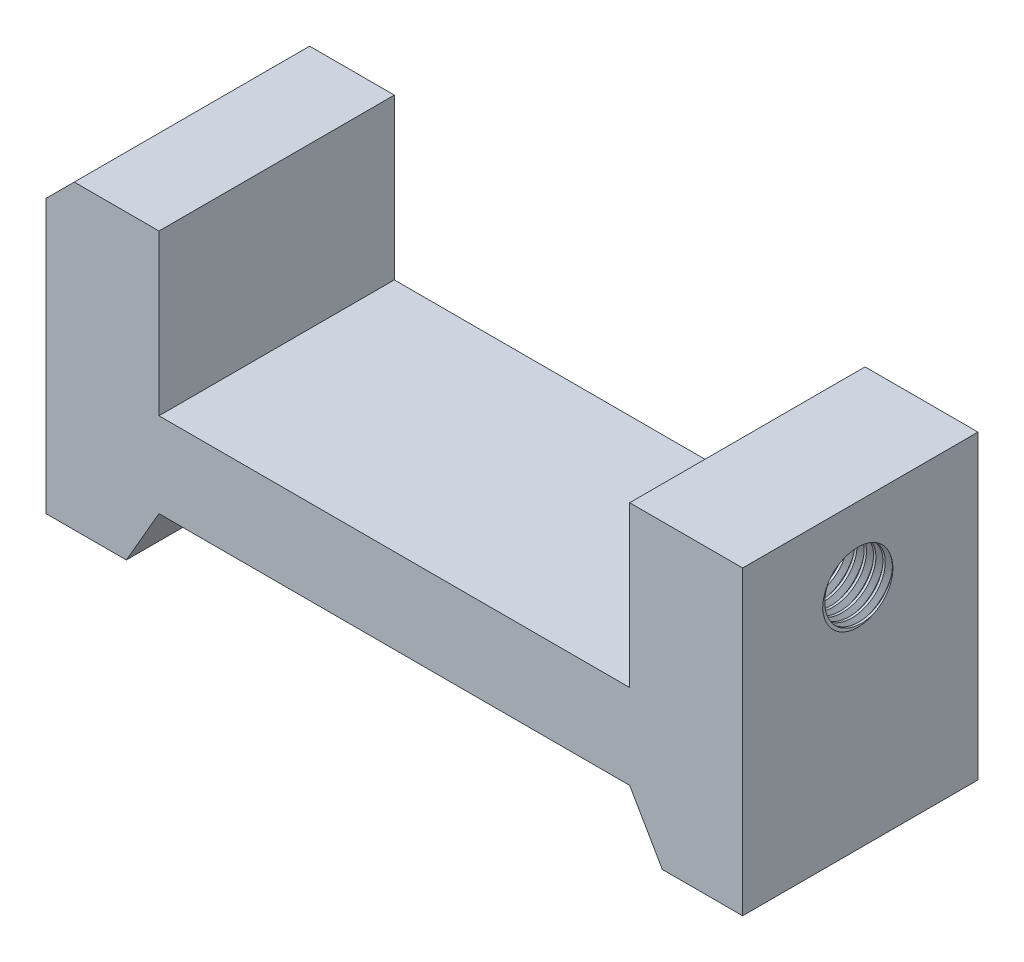
SolidWorks part; units mm, degrees
ref_plane "Front Plane" through (0, 0, 0) normal (0, 0, 1) x (1, 0, 0)
ref_plane "Top Plane" through (0, 0, 0) normal (0, 1, 0) x (1, 0, 0)
ref_plane "Right Plane" through (0, 0, 0) normal (1, 0, 0) x (0, 0, -1)
sketch "Sketch1" plane through (0, 0, 0) normal (0, 0, 1) x (1, 0, 0)
  line L0 (-25, 0) -> (-25, 17)
  line L1 (25, 0) -> (-25, 0)
  line L5 (-25, 17) -> (-37, 17)
  line L6 (-37, 17) -> (-37, -15)
  line L7 (-37, -15) -> (-28.4641, -15)
  line L9 (25, 0) -> (25, 17)
  line L10 (25, 17) -> (37, 17)
  line L11 (37, 17) -> (37, -15)
  line L14 (47.5824, 0) -> (-47.5824, 0) construction
  line L16 (-25, -9) -> (25, -9)
  line L17 (-28.4641, -15) -> (-25, -9)
  line L18 (37, -15) -> (28.4641, -15)
  line L19 (28.4641, -15) -> (25, -9)
  point P0 (0, 0)
  point P17 (0, 0)
  point P19 (0, 0)
  dimension "D1" = 50
  dimension "D2" = 12
  dimension "D3" = 30
  dimension "D4" = 30
  dimension "D5" = 6
  dimension "D6" = 9
  dimension "D7" = 32
  dimension "D8" = 12
extrude "Boss-Extrude1" add sketch "Sketch1" against normal blind 25
chamfer "Chamfer1" distance 3 angle 45 1 edges at (-37, 17, -12.5)
hole_wizard "Ø8.0mm Dowel Hole2" positions "Sketch2" profile "Sketch4" hole size "Ø8.0" standard "ANSI Metric"
sketch "Sketch2" plane through (37, 0, 0) normal (1, 0, 0) x (0, 0, -1)
  line L0 (25, 17) -> (0, 17) construction
  point P0 (12.5, 9)
  dimension "D1" = 8
  dimension "D2" = 12.5
sketch "Sketch4" plane through (37, 9, -12.5) normal (0, 1, 0) x (0, 0, -1)
  line L0 (0, 0) -> (0, 14.4024)
  line L1 (0, 14.4024) -> (4, 11.999)
  line L2 (4, 11.999) -> (4, 0)
  line L5 (4, 0) -> (0, 0)
  line L10 (0, 14.4024) -> (-4, 11.999) construction
  line L11 (0, -6.35) -> (0, 107.95) construction
  dimension "Hole Dia." = 8
  dimension "Hole Depth" = 11.999
  dimension "Drill Angle" = 118
thread "Thread1" pitch 1 method extrude trim with start face yes trim with end face yes profile "Thread Profile1" start angle 0, offset 1, length 0, pitch 1, diameter 8
ref_plane "Plane1" through (38, 9, -8.5) normal (0, -1, 0) x (0, 0, 1)
sketch "Thread Profile1" plane through (38, 9, -8.5) normal (0, -1, 0) x (0, 0, 1)
  line L0 (0, 0) -> (0, 1) construction
  line L11 (0, 0) -> (0, 0.875)
  line L12 (0, 0.875) -> (-0.5413, 0.5625)
  line L13 (-0.5413, 0.5625) -> (-0.5413, 0.3125)
  line L15 (-0.5413, 0.3125) -> (0, 0)
  line L17 (-0.5413, 0.4375) -> (0, 0.4375) construction
  point P2 (0, 0)
  dimension "Pitch" = 1
  dimension "Profile_Angle" = 60
  dimension "Profile_Land" = 0.25
  dimension "Profile_Height" = 0.5413
